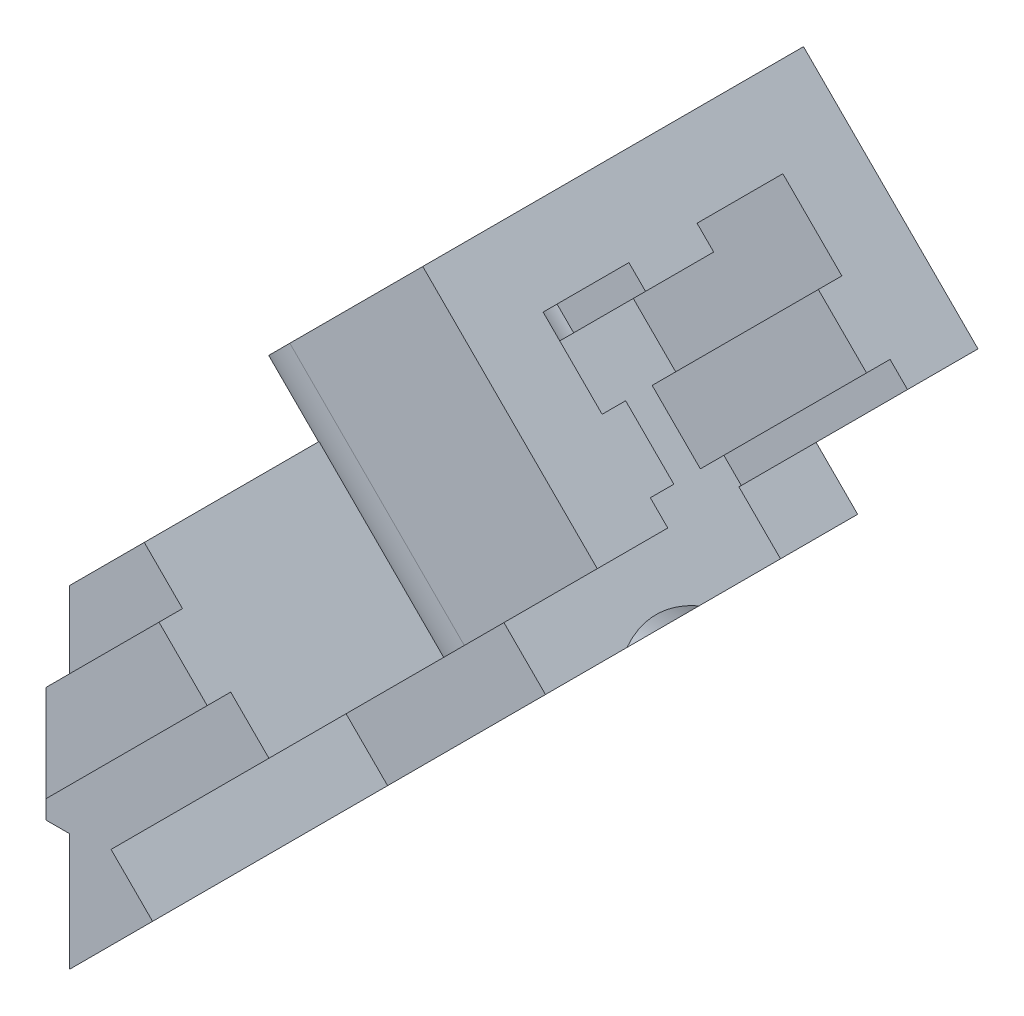
SolidWorks part; units mm, degrees
ref_plane "Front Plane" through (0, 0, 0) normal (0, 0, 1) x (1, 0, 0)
ref_plane "Top Plane" through (0, 0, 0) normal (0, 1, 0) x (1, 0, 0)
ref_plane "Right Plane" through (0, 0, 0) normal (1, 0, 0) x (0, 0, -1)
sketch "Esquisse1" plane through (0, 0, 0) normal (0, 0, 1) x (1, 0, 0)
  line L0 (0, 0) -> (0, 5)
  line L1 (0, 5) -> (-1, 5)
  line L2 (-1, 5) -> (-1, 7.9)
  line L3 (-1, 7.9) -> (0, 7.9)
  line L4 (0, 7.9) -> (0, 14.1421)
  line L5 (0, 14.1421) -> (3.182, 17.3241)
  line L6 (3.182, 17.3241) -> (10.253, 10.253)
  line L7 (10.253, 10.253) -> (0, 0)
  dimension "D1" = 2.9
  dimension "D2" = 45
  dimension "D3" = 10
  dimension "D4" = 5
  dimension "D5" = 1
  dimension "D6" = 14.5
extrude "Main Extrusion" add sketch "Esquisse1" along normal mid plane 30
sketch "Esquisse2" plane through (0, 0, 0) normal (0.7071, -0.7071, 0) x (0, 0, -1)
  line L0 (15, 0) -> (15, 14.5) construction
  line L1 (5, 5) -> (15, 5)
  line L2 (5, 5) -> (5, 14.5)
  line L3 (5, 14.5) -> (15, 14.5)
  line L4 (15, 5) -> (15, 14.5)
  line L5 (-15, 14.5) -> (15, 14.5) construction
  line L6 (-15, 0) -> (15, 0) construction
  dimension "D1" = 5
  dimension "D2" = 10
extrude "Window Extrusion" cut sketch "Esquisse2" against normal blind 2.5
sketch "Esquisse5" plane through (-1.7678, 1.7678, 0) normal (0.7071, -0.7071, 0) x (0, 0, -1)
  line L0 (15, 14.5) -> (5, 14.5) construction
  line L2 (5, 5) -> (15, 5) construction
  circle A0 centre (10, 11.5) radius 1.25
  point P4 (10, 14.5)
  dimension "D1" = 2.5
  dimension "D2" = 6.5
extrude "Window Hole Extrusion" cut sketch "Esquisse5" against normal through all
sketch "Esquisse7" plane through (10.253, 10.253, 0) normal (0.7071, 0.7071, 0) x (0, 0, -1)
  line L0 (-5.1, 2.5) -> (-5.1, 3.55)
  line L1 (-5.1, 3.55) -> (-4.1, 3.55)
  line L2 (-4.1, 3.55) -> (-4.1, 6.45)
  line L3 (-4.1, 6.45) -> (-5.1, 6.45)
  line L4 (-5.1, 6.45) -> (-5.1, 10)
  line L6 (-15, 10) -> (15, 10) construction
  line L7 (-15, 0) -> (-15, 10) construction
  line L18 (-8.1, 10) -> (-5.1, 10)
  line L19 (-8.1, 10) -> (-8.1, 2.5)
  line L20 (-8.1, 2.5) -> (-5.1, 2.5)
  dimension "D1" = 1
  dimension "D2" = 2.9
  dimension "D3" = 3
  dimension "D4" = 6.9
  dimension "D5" = 3.55
  dimension "D6" = 7.5
extrude "Fixation Top MakerBeam Extrusion" add sketch "Esquisse7" along normal blind 10
mirror "Window Symetry" about plane through (0, 0, 0) normal (0, 0, 1) of "Fixation Top MakerBeam Extrusion", "Window Extrusion", "Window Hole Extrusion"
sketch "Esquisse3" plane through (-1, 0, 0) normal (-1, 0, 0) x (0, 0, 1)
  line L0 (15, 7.9) -> (15, 5) construction
  line L1 (0, -55) -> (0, 55) construction
  circle A0 centre (0, 6.45) radius 1.5
  point P5 (15, 6.45)
  dimension "D1" = 3
extrude "Window Hole Fixation" cut sketch "Esquisse3" against normal through all
ref_plane "Plan1" through (3, 0, 0) normal (-1, 0, 0) x (0, 0, 1)
sketch "Esquisse4" plane through (3, 0, 0) normal (-1, 0, 0) x (0, 0, 1)
  circle A0 centre (0, 6.45) radius 4.1
  arc A1 (0.3841, 5) -> (0.3841, 7.9) centre (0, 6.45) ccw construction
  dimension "D1" = 8.2
extrude "Central Fixation" cut sketch "Esquisse4" against normal through all
sketch "Esquisse6" plane through (0, 0, 15) normal (0, 0, 1) x (1, 0, 0)
  line L0 (0, 10.8894) -> (4.8083, 15.6978)
  line L1 (8.4853, 12.0208) -> (3.182, 17.3241) construction
  line L2 (4.8083, 15.6978) -> (6.8589, 13.6472)
  line L3 (6.8589, 13.6472) -> (0, 6.7882)
  line L4 (0, 6.7882) -> (0, 10.8894)
  line L5 (0, 5) -> (0, 0) construction
  point P6 (5.8336, 14.6725)
  point P7 (5.8336, 14.6725)
  dimension "D1" = 2.9
extrude "Boss.-Extru.2" add sketch "Esquisse6" along normal blind 1
sketch "Esquisse8" plane through (17.3241, 17.3241, 0) normal (0.7071, 0.7071, 0) x (0, 0, -1)
  line L0 (-8.1, 10) -> (-1.45, 10)
  line L1 (-1.45, 10) -> (-1.45, 9)
  line L2 (-1.45, 9) -> (1.45, 9)
  line L3 (1.45, 9) -> (1.45, 10)
  line L4 (1.45, 10) -> (8.1, 10)
  line L5 (8.1, 10) -> (8.1, 13)
  line L6 (8.1, 13) -> (-8.1, 13)
  line L7 (-8.1, 13) -> (-8.1, 10)
  line L8 (0, 55) -> (0, -55) construction
  point P9 (0, 9)
  dimension "D1" = 3
  dimension "D2" = 2.9
  dimension "D3" = 1
extrude "Boss.-Extru.6" add sketch "Esquisse8" against normal blind 12
fillet "Congé1" radius 4 2 edges at (0.7071, 16.9706, -8.1) (0.7071, 16.9706, 8.1)
sketch "Esquisse10" plane through (0, 0, -4.1) normal (0, 0, 1) x (1, 0, 0)
  line L0 (8.1317, 26.5165) -> (15.5563, 19.0919) construction
  line L3 (15.5563, 19.0919) -> (8.4853, 12.0208) construction
  circle A0 centre (10.253, 17.3241) radius 1.6
  dimension "D1" = 3.2
  dimension "D2" = 5
  dimension "D3" = 2.5
sketch "Esquisse11" plane through (-9.1924, 9.1924, 0) normal (-0.7071, 0.7071, 0) x (0, 0, 1)
  line L0 (-8.1, 24.5) -> (8.1, 24.5) construction
  circle A0 centre (0, 19.5) radius 1.6
  point P4 (0, 24.5)
  dimension "D1" = 3.2
  dimension "D2" = 5
extrude "Enlèv. mat.-Extru.2" cut sketch "Esquisse11" against normal through all
